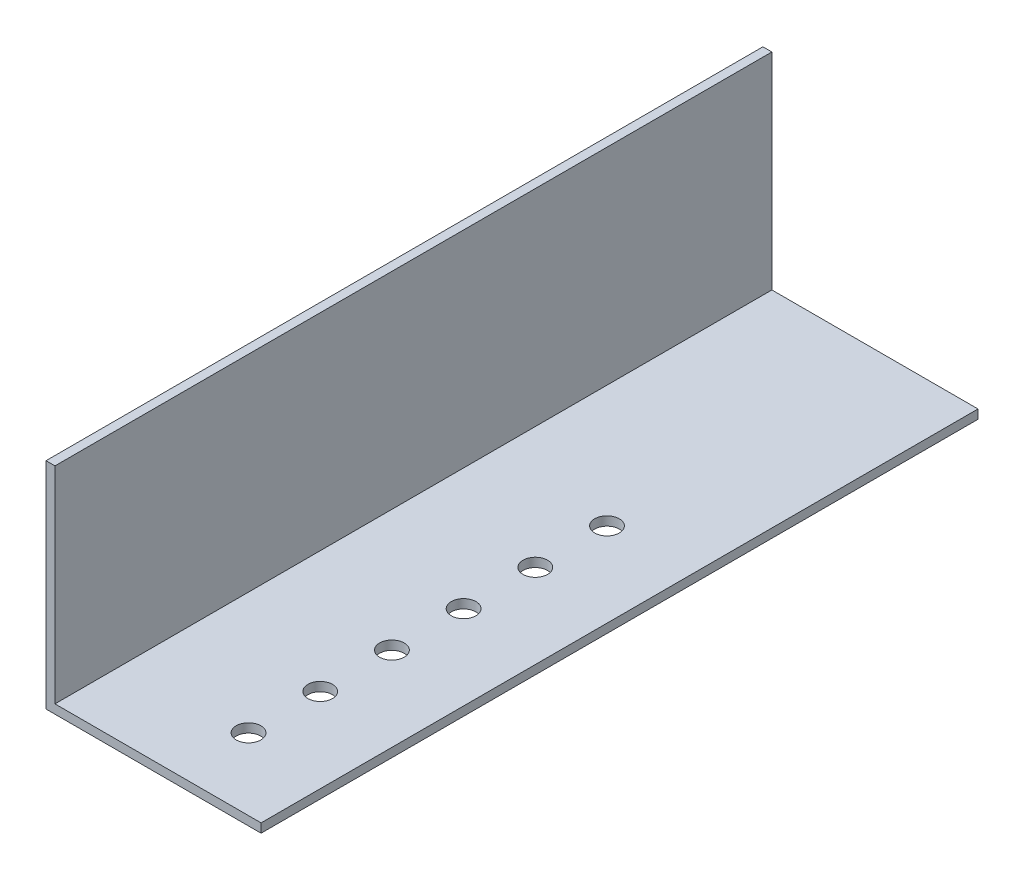
SolidWorks part; units mm, degrees
ref_plane "Front Plane" through (0, 0, 0) normal (0, 0, 1) x (1, 0, 0)
ref_plane "Top Plane" through (0, 0, 0) normal (0, 1, 0) x (1, 0, 0)
ref_plane "Right Plane" through (0, 0, 0) normal (1, 0, 0) x (0, 0, -1)
sketch "Sketch1" plane through (0, 0, 0) normal (0, 0, 1) x (1, 0, 0)
  line L0 (0, 0) -> (0, 38.1)
  line L1 (0, 38.1) -> (1.5875, 38.1)
  line L2 (1.5875, 38.1) -> (1.5875, 1.5875)
  line L3 (1.5875, 1.5875) -> (38.1, 1.5875)
  line L4 (38.1, 1.5875) -> (38.1, 0)
  line L5 (38.1, 0) -> (0, 0)
  dimension "D1" = 38.1
  dimension "D2" = 1.5875
extrude "Boss-Extrude1" add sketch "Sketch1" along normal blind 127
sketch "Sketch2" plane through (0, 1.5875, 0) normal (0, 1, 0) x (1, 0, 0)
  line L0 (23.1775, -127) -> (23.1775, 0) construction
  line L1 (38.1, -127) -> (1.5875, -127) construction
  line L3 (1.5875, -127) -> (1.5875, 0) construction
  circle A0 centre (23.1775, -114.3) radius 2.1828
  circle A1 centre (23.1775, -101.6) radius 2.1828
  circle A2 centre (23.1775, -88.9) radius 2.1828
  circle A3 centre (23.1775, -76.2) radius 2.1828
  circle A4 centre (23.1775, -63.5) radius 2.1828
  circle A5 centre (23.1775, -50.8) radius 2.1828
  dimension "D1" = 4.3656
  dimension "D2" = 12.7
  dimension "D5" = 12.7
  dimension "D6" = 12.7
  dimension "D7" = 12.7
  dimension "D3" = 12.7
  dimension "D4" = 12.7
  dimension "D8" = 21.59
extrude "Cut-Extrude1" cut sketch "Sketch2" against normal blind 127
